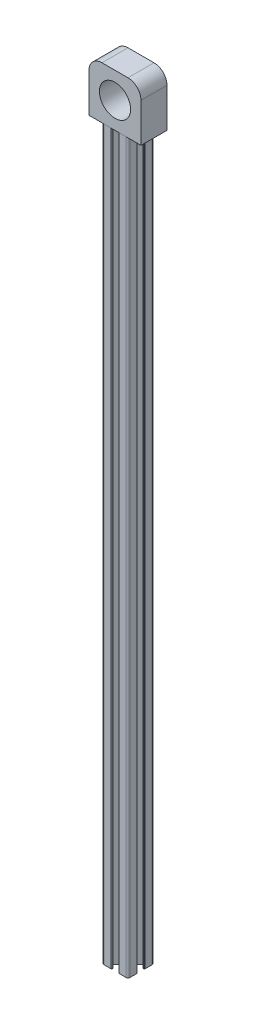
SolidWorks part; units mm, degrees
material "6061-O (SS)"
ref_plane "Front Plane" through (0, 0, 0) normal (0, 0, 1) x (1, 0, 0)
ref_plane "Top Plane" through (0, 0, 0) normal (0, 1, 0) x (1, 0, 0)
ref_plane "Right Plane" through (0, 0, 0) normal (1, 0, 0) x (0, 0, -1)
sketch "Sketch1" plane through (0, 0, 0) normal (0, 1, 0) x (1, 0, 0)
  line L0 (9.4949, 2.6581) -> (9.0109, 2.6581)
  line L1 (8.5029, 3.1661) -> (8.5029, 5.5151)
  line L2 (10.0029, 3.1661) -> (10.0029, 8.5281)
  line L3 (3.6579, -2.3558) -> (3.6579, 2.412)
  line L4 (7.269, 6.0231) -> (7.9949, 6.0231)
  line L5 (6.9098, 5.8743) -> (3.8067, 2.7712)
  line L6 (9.4949, -2.6019) -> (9.0109, -2.6019)
  line L7 (10.0029, -3.1099) -> (10.0029, -8.4719)
  line L8 (8.5029, -3.1099) -> (8.5029, -5.4589)
  line L9 (7.269, -5.9669) -> (7.9949, -5.9669)
  line L10 (6.9098, -5.8181) -> (3.8067, -2.715)
  line L11 (2.1278, -2.2764) -> (2.3074, -2.0968)
  line L12 (-2.6271, 9.5201) -> (-2.6271, 9.0361)
  line L13 (-3.1351, 10.0281) -> (-8.4971, 10.0281)
  line L14 (-3.1351, 8.5281) -> (-5.4841, 8.5281)
  line L15 (2.3868, 3.6831) -> (-2.381, 3.6831)
  line L16 (-5.9921, 7.2942) -> (-5.9921, 8.0201)
  line L17 (-5.8433, 6.935) -> (-2.7402, 3.8319)
  line L18 (2.6329, 9.5201) -> (2.6329, 9.0361)
  line L19 (3.1409, 10.0281) -> (8.5029, 10.0281)
  line L20 (3.1409, 8.5281) -> (5.4899, 8.5281)
  line L21 (5.9979, 7.2942) -> (5.9979, 8.0201)
  line L22 (5.8491, 6.935) -> (2.746, 3.8319)
  line L23 (2.3074, 2.153) -> (2.1278, 2.3326)
  line L24 (-9.4891, -2.6019) -> (-9.0051, -2.6019)
  line L25 (-9.9971, -3.1099) -> (-9.9971, -8.4719)
  line L26 (-8.4971, -3.1099) -> (-8.4971, -5.4589)
  line L27 (-3.6521, 2.412) -> (-3.6521, -2.3558)
  line L28 (-7.2632, -5.9669) -> (-7.9891, -5.9669)
  line L29 (-6.904, -5.8181) -> (-3.8009, -2.715)
  line L30 (-9.4891, 2.6581) -> (-9.0051, 2.6581)
  line L31 (-9.9971, 3.1661) -> (-9.9971, 8.5281)
  line L32 (-8.4971, 3.1661) -> (-8.4971, 5.5151)
  line L33 (-7.2632, 6.0231) -> (-7.9891, 6.0231)
  line L34 (-6.904, 5.8743) -> (-3.8009, 2.7712)
  line L35 (-2.122, 2.3326) -> (-2.3016, 2.153)
  line L36 (2.6329, -9.4639) -> (2.6329, -8.9799)
  line L37 (3.1409, -9.9719) -> (8.5029, -9.9719)
  line L38 (3.1409, -8.4719) -> (5.4899, -8.4719)
  line L39 (-2.381, -3.6269) -> (2.3868, -3.6269)
  line L40 (5.9979, -7.238) -> (5.9979, -7.9639)
  line L41 (5.8491, -6.8788) -> (2.746, -3.7757)
  line L42 (-2.6271, -9.4639) -> (-2.6271, -8.9799)
  line L43 (-3.1351, -9.9719) -> (-8.4971, -9.9719)
  line L44 (-3.1351, -8.4719) -> (-5.4841, -8.4719)
  line L45 (-5.9921, -7.238) -> (-5.9921, -7.9639)
  line L46 (-5.8433, -6.8788) -> (-2.7402, -3.7757)
  line L47 (-2.3016, -2.0968) -> (-2.122, -2.2764)
  arc A0 (-0.8011, -1.9071) -> (0.8069, -1.9071) centre (0.0029, 0.0281) ccw
  arc A1 (8.5029, 5.5151) -> (7.9949, 6.0231) centre (7.9949, 5.5151) ccw
  arc A2 (7.269, 6.0231) -> (6.9098, 5.8743) centre (7.269, 5.5151) ccw
  arc A3 (3.8067, 2.7712) -> (3.6579, 2.412) centre (4.1659, 2.412) ccw
  arc A4 (3.6579, -2.3558) -> (3.8067, -2.715) centre (4.1659, -2.3558) ccw
  arc A5 (6.9098, -5.8181) -> (7.269, -5.9669) centre (7.269, -5.4589) ccw
  arc A6 (7.9949, -5.9669) -> (8.5029, -5.4589) centre (7.9949, -5.4589) ccw
  arc A7 (9.0109, -2.6019) -> (8.5029, -3.1099) centre (9.0109, -3.1099) ccw
  arc A8 (10.0029, -3.1099) -> (9.4949, -2.6019) centre (9.4949, -3.1099) ccw
  arc A9 (9.4949, 2.6581) -> (10.0029, 3.1661) centre (9.4949, 3.1661) ccw
  arc A10 (8.5029, 3.1661) -> (9.0109, 2.6581) centre (9.0109, 3.1661) ccw
  arc A11 (0.8069, -1.9071) -> (2.1278, -2.2764) centre (1.5713, -1.7199) ccw
  arc A12 (2.3074, -2.0968) -> (1.9381, -0.7759) centre (1.7509, -1.5403) ccw
  arc A13 (-2.6271, 9.5201) -> (-3.1351, 10.0281) centre (-3.1351, 9.5201) ccw
  arc A14 (-3.1351, 8.5281) -> (-2.6271, 9.0361) centre (-3.1351, 9.0361) ccw
  arc A15 (1.9381, -0.7759) -> (1.9381, 0.8321) centre (0.0029, 0.0281) ccw
  arc A16 (-2.7402, 3.8319) -> (-2.381, 3.6831) centre (-2.381, 4.1911) ccw
  arc A17 (-5.4841, 8.5281) -> (-5.9921, 8.0201) centre (-5.4841, 8.0201) ccw
  arc A18 (-5.9921, 7.2942) -> (-5.8433, 6.935) centre (-5.4841, 7.2942) ccw
  arc A19 (2.6329, 9.0361) -> (3.1409, 8.5281) centre (3.1409, 9.0361) ccw
  arc A20 (3.1409, 10.0281) -> (2.6329, 9.5201) centre (3.1409, 9.5201) ccw
  arc A21 (5.9979, 8.0201) -> (5.4899, 8.5281) centre (5.4899, 8.0201) ccw
  arc A22 (5.8491, 6.935) -> (5.9979, 7.2942) centre (5.4899, 7.2942) ccw
  arc A23 (2.3868, 3.6831) -> (2.746, 3.8319) centre (2.3868, 4.1911) ccw
  arc A24 (1.9381, 0.8321) -> (2.3074, 2.153) centre (1.7509, 1.5965) ccw
  arc A25 (2.1278, 2.3326) -> (0.8069, 1.9632) centre (1.5713, 1.7761) ccw
  arc A26 (-9.4891, -2.6019) -> (-9.9971, -3.1099) centre (-9.4891, -3.1099) ccw
  arc A27 (-8.4971, -3.1099) -> (-9.0051, -2.6019) centre (-9.0051, -3.1099) ccw
  arc A28 (0.8069, 1.9632) -> (-0.8011, 1.9632) centre (0.0029, 0.0281) ccw
  arc A29 (-3.8009, -2.715) -> (-3.6521, -2.3558) centre (-4.1601, -2.3558) ccw
  arc A30 (-8.4971, -5.4589) -> (-7.9891, -5.9669) centre (-7.9891, -5.4589) ccw
  arc A31 (-7.2632, -5.9669) -> (-6.904, -5.8181) centre (-7.2632, -5.4589) ccw
  arc A32 (-9.0051, 2.6581) -> (-8.4971, 3.1661) centre (-9.0051, 3.1661) ccw
  arc A33 (-9.9971, 3.1661) -> (-9.4891, 2.6581) centre (-9.4891, 3.1661) ccw
  arc A34 (-7.9891, 6.0231) -> (-8.4971, 5.5151) centre (-7.9891, 5.5151) ccw
  arc A35 (-6.904, 5.8743) -> (-7.2632, 6.0231) centre (-7.2632, 5.5151) ccw
  arc A36 (-3.6521, 2.412) -> (-3.8009, 2.7712) centre (-4.1601, 2.412) ccw
  arc A37 (-0.8011, 1.9632) -> (-2.122, 2.3326) centre (-1.5655, 1.7761) ccw
  arc A38 (-2.3016, 2.153) -> (-1.9322, 0.8321) centre (-1.7451, 1.5965) ccw
  arc A39 (2.6329, -9.4639) -> (3.1409, -9.9719) centre (3.1409, -9.4639) ccw
  arc A40 (3.1409, -8.4719) -> (2.6329, -8.9799) centre (3.1409, -8.9799) ccw
  arc A41 (-1.9322, 0.8321) -> (-1.9322, -0.7759) centre (0.0029, 0.0281) ccw
  arc A42 (2.746, -3.7757) -> (2.3868, -3.6269) centre (2.3868, -4.1349) ccw
  arc A43 (5.4899, -8.4719) -> (5.9979, -7.9639) centre (5.4899, -7.9639) ccw
  arc A44 (5.9979, -7.238) -> (5.8491, -6.8788) centre (5.4899, -7.238) ccw
  arc A45 (-2.6271, -8.9799) -> (-3.1351, -8.4719) centre (-3.1351, -8.9799) ccw
  arc A46 (-3.1351, -9.9719) -> (-2.6271, -9.4639) centre (-3.1351, -9.4639) ccw
  arc A47 (-5.9921, -7.9639) -> (-5.4841, -8.4719) centre (-5.4841, -7.9639) ccw
  arc A48 (-5.8433, -6.8788) -> (-5.9921, -7.238) centre (-5.4841, -7.238) ccw
  arc A49 (-2.381, -3.6269) -> (-2.7402, -3.7757) centre (-2.381, -4.1349) ccw
  arc A50 (-1.9322, -0.7759) -> (-2.3016, -2.0968) centre (-1.7451, -1.5403) ccw
  arc A51 (-2.122, -2.2764) -> (-0.8011, -1.9071) centre (-1.5655, -1.7199) ccw
  arc A52 (10.0029, 8.5281) -> (8.5029, 10.0281) centre (8.5029, 8.5281) ccw
  arc A53 (8.5029, -9.9719) -> (10.0029, -8.4719) centre (8.5029, -8.4719) ccw
  arc A54 (-9.9971, -8.4719) -> (-8.4971, -9.9719) centre (-8.4971, -8.4719) ccw
  arc A55 (-8.4971, 10.0281) -> (-9.9971, 8.5281) centre (-8.4971, 8.5281) ccw
extrude "Boss-Extrude1" add sketch "Sketch1" along normal blind 560
sketch "Sketch2" plane through (0, 560, 0) normal (0, 1, 0) x (1, 0, 0)
  line L1 (-20, -10) -> (20, -10)
  line L2 (-20, -10) -> (-20, 10)
  line L3 (-20, 10) -> (20, 10)
  line L4 (20, -10) -> (20, 10)
  line L5 (-20, -10) -> (20, 10) construction
  line L6 (-20, 10) -> (20, -10) construction
  point P0 (0, 0)
  dimension "D1" = 20
extrude "Hinge Box" add sketch "Sketch2" along normal blind 40
fillet "Fillet1" radius 10 2 edges at (-20, 600, 0) (20, 600, 0)
sketch "Sketch3" plane through (0, 0, 10) normal (0, 0, 1) x (1, 0, 0)
  line L0 (0, 560) -> (0, 600) construction
  line L3 (-20, 560) -> (20, 560) construction
  line L4 (-10, 600) -> (10, 600) construction
  circle A0 centre (0, 580) radius 12
  dimension "D1" = 24
extrude "Hinge Hole" cut sketch "Sketch3" against normal blind 40
